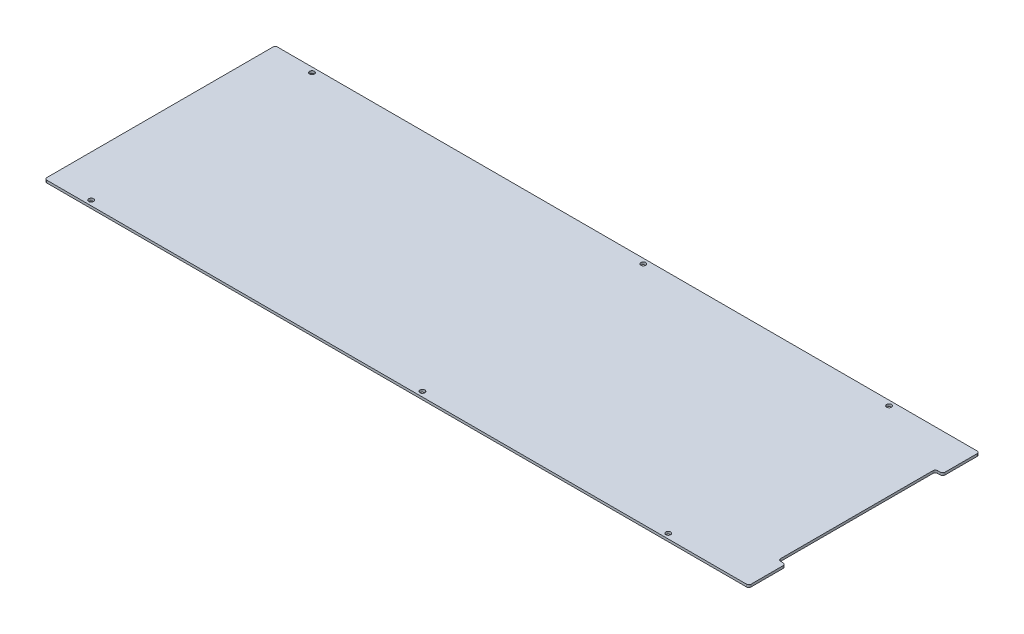
SolidWorks part; units mm, degrees
ref_plane "Front Plane" through (0, 0, 0) normal (0, 0, 1) x (1, 0, 0)
ref_plane "Top Plane" through (0, 0, 0) normal (0, 1, 0) x (1, 0, 0)
ref_plane "Right Plane" through (0, 0, 0) normal (1, 0, 0) x (0, 0, -1)
sketch "Sketch1" plane through (0, 0, 0) normal (0, 1, 0) x (1, 0, 0)
  line L1 (-455.6125, -149.225) -> (455.6125, -149.225)
  line L2 (-455.6125, -149.225) -> (-455.6125, 149.225)
  line L3 (-455.6125, 149.225) -> (455.6125, 149.225)
  line L4 (455.6125, -149.225) -> (455.6125, 149.225)
  line L5 (-455.6125, -149.225) -> (455.6125, 149.225) construction
  line L6 (-455.6125, 149.225) -> (455.6125, -149.225) construction
  point P0 (0, 0)
  dimension "D1" = 911.225
  dimension "D2" = 298.45
extrude "Boss-Extrude1" add sketch "Sketch1" along normal blind 3.175
sketch "Sketch2" plane through (0, 3.175, 0) normal (0, 1, 0) x (1, 0, 0)
  line L0 (455.6125, -149.225) -> (455.6125, 149.225) construction
  line L1 (455.6125, 101.6) -> (446.0875, 101.6)
  line L2 (455.6125, 101.6) -> (455.6125, -101.6)
  line L3 (455.6125, -101.6) -> (446.0875, -101.6)
  line L4 (446.0875, 101.6) -> (446.0875, -101.6)
  point P6 (446.0875, 0)
  dimension "D1" = 203.2
  dimension "D2" = 9.525
extrude "Cut-Extrude1" cut sketch "Sketch2" against normal through all
fillet "Fillet1" radius 3.175 2 edges at (446.0875, 1.5875, 101.6) (446.0875, 1.5875, -101.6)
hole_wizard "1/4 (0.25) Diameter Hole1" positions "Sketch3" profile "Sketch4" hole size "1/4" standard "ANSI Inch" end condition through all
sketch "Sketch3" plane through (0, 0, 0) normal (0, -1, 0) x (-1, 0, 0)
  line L0 (-455.6125, 149.225) -> (455.6125, 149.225) construction
  line L1 (455.6125, 149.225) -> (455.6125, -149.225) construction
  point P0 (-345.0488, 142.875)
  point P2 (401.6375, 142.875)
  point P4 (-26.9875, 142.875)
  dimension "D1" = 6.35
  dimension "D2" = 53.975
  dimension "D3" = 482.6
  dimension "D4" = 800.6613
sketch "Sketch4" plane through (345.0488, 0, -142.875) normal (1, 0, 0) x (0, 0, -1)
  line L0 (0, 0) -> (0, 3.175)
  line L1 (0, 3.175) -> (3.175, 3.175)
  line L2 (3.175, 3.175) -> (3.175, 0)
  line L5 (3.175, 0) -> (0, 0)
  line L11 (0, -6.35) -> (0, 107.95) construction
  dimension "Thru Hole Dia." = 6.35
  dimension "Thru Hole Depth" = 3.175
mirror "Mirror1" about plane through (0, 0, 0) normal (0, 0, 1) of "1/4 (0.25) Diameter Hole1"
fillet "Fillet2" radius 3.175 6 edges at (-455.6125, 1.5875, 149.225) (-455.6125, 1.5875, -149.225) (455.6125, 1.5875, 149.225) (455.6125, 1.5875, 101.6) (455.6125, 1.5875, -101.6) (455.6125, 1.5875, -149.225)
